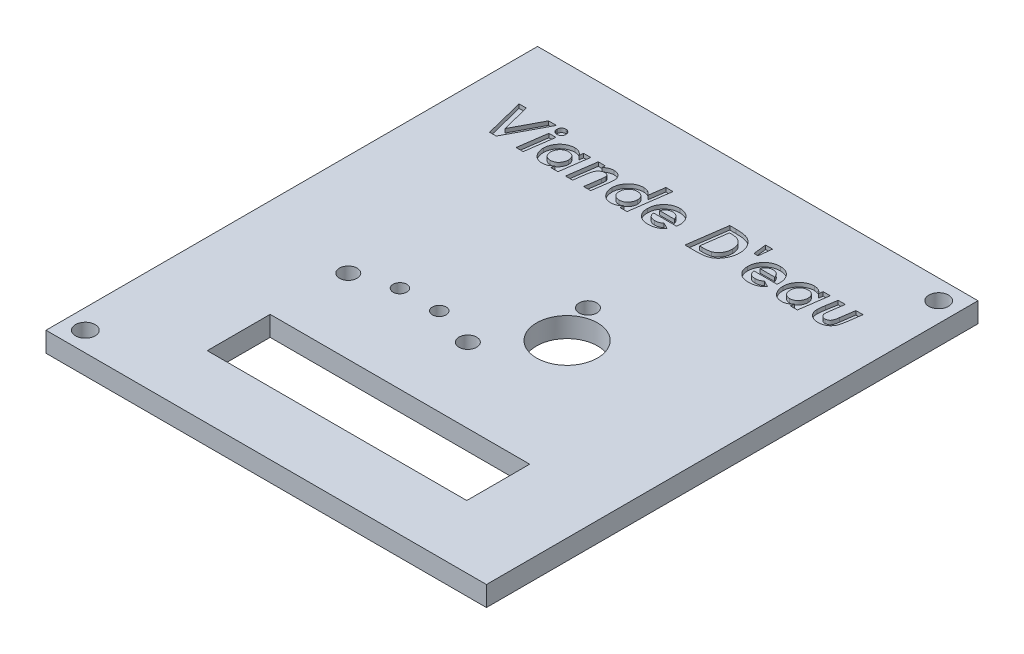
SolidWorks part; units mm, degrees
ref_plane "Front Plane" through (0, 0, 0) normal (0, 0, 1) x (1, 0, 0)
ref_plane "Top Plane" through (0, 0, 0) normal (0, 1, 0) x (1, 0, 0)
ref_plane "Right Plane" through (0, 0, 0) normal (1, 0, 0) x (0, 0, -1)
sketch "Sketch1" plane through (0, 0, 0) normal (0, 1, 0) x (1, 0, 0)
  line L1 (-56, -62.5) -> (56, -62.5)
  line L2 (-56, -62.5) -> (-56, 62.5)
  line L3 (-56, 62.5) -> (56, 62.5)
  line L4 (56, -62.5) -> (56, 62.5)
  line L5 (-56, -62.5) -> (56, 62.5) construction
  line L6 (-56, 62.5) -> (56, -62.5) construction
  point P0 (0, 0)
  dimension "D1" = 112
  dimension "D2" = 125
extrude "Boss-Extrude1" add sketch "Sketch1" along normal blind 5.08
sketch "Sketch5" plane through (0, 5.08, 0) normal (0, 1, 0) x (1, 0, 0)
  line L0 (-56, -62.5) -> (56, -62.5) construction
  line L1 (-31, -46.5) -> (35, -46.5)
  line L2 (-31, -46.5) -> (-31, -30.5)
  line L3 (-31, -30.5) -> (35, -30.5)
  line L4 (35, -46.5) -> (35, -30.5)
  line L5 (-31, -46.5) -> (35, -30.5) construction
  line L6 (-31, -30.5) -> (35, -46.5) construction
  line L10 (-56, 62.5) -> (-56, -62.5) construction
  circle A0 centre (12.5, 1.5) radius 7.75
  circle A1 centre (-30.13, -11.51) radius 2.25
  circle A2 centre (-20.25, -8.2495) radius 1.75
  circle A3 centre (-10.25, -8.2495) radius 1.75
  circle A4 centre (0.2695, -11.51) radius 2.25
  circle A5 centre (8.001, 11.311) radius 2.25
  point P0 (2, -38.5)
  dimension "D4" = 15.5
  dimension "D8" = 4.5
  dimension "D9" = 3.5
  dimension "D5" = 47.999
  dimension "D6" = 51.189
  dimension "D10" = 43.5
  dimension "D12" = 55.7305
  dimension "D13" = 74.01
  dimension "D14" = 66.25
  dimension "D15" = 70.7495
  dimension "D16" = 70.7495
  dimension "D17" = 76.25
  dimension "D18" = 86.13
  dimension "D19" = 74.01
  dimension "D1" = 66
  dimension "D2" = 16
  dimension "D3" = 16
  dimension "D7" = 25
  dimension "D11" = 61
extrude "Cut-Extrude1" cut sketch "Sketch5" against normal up to next contours A0 | A4 | A3 | A2 | A1 | L1 L4 L3 L2 | A5 region at (2, 5.08, 38.5) region at (12.5, 5.08, -1.5) region at (-30.13, 5.08, 11.51) region at (-20.25, 5.08, 8.2495) region at (-10.25, 5.08, 8.2495) region at (0.2695, 5.08, 11.51) region at (8.001, 5.08, -11.311)
sketch "Sketch7" plane through (0, 5.08, 0) normal (0, 1, 0) x (1, 0, 0)
  line L5 (56, 62.5) -> (-56, 62.5) construction
  line L6 (56, -62.5) -> (56, 62.5) construction
  line L7 (-56, -62.5) -> (56, -62.5) construction
  line L8 (-56, 62.5) -> (-56, -62.5) construction
  circle A0 centre (-51, -57.5) radius 2.5
  circle A1 centre (51, 57.5) radius 2.5
  dimension "D2" = 5
  dimension "D4" = 5
  dimension "D3" = 5
  dimension "D5" = 5
  dimension "D6" = 5
extrude "Cut-Extrude3" cut sketch "Sketch7" against normal blind 4
sketch "Sketch8" plane through (0, 5.08, 0) normal (0, 1, 0) x (1, 0, 0)
  line L0 (-56, 37.5) -> (56, 37.5) construction
  line L1 (56, 62.5) -> (-56, 62.5) construction
  line L2 (-56, 62.5) -> (-56, -62.5) construction
  text T0 "<b><i>Viande D'eau</i></b>" font "Century Gothic" height 10
  point P1 (0, 37.5)
  point P7 (0, 62.5)
  dimension "D1" = 25
extrude "Cut-Extrude4" cut sketch "Sketch8" against normal blind 1
